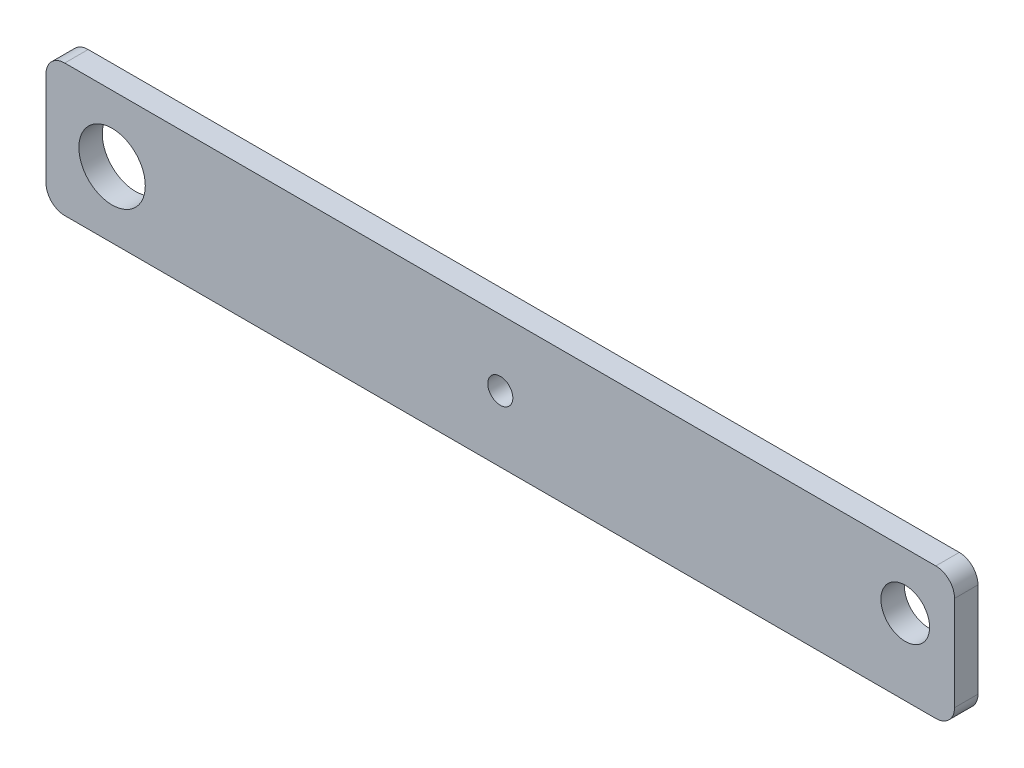
SolidWorks part; units mm, degrees
material "1100-H12 Rod (SS)"
ref_plane "X-Y Datum" through (0, 0, 0) normal (0, 0, 1) x (1, 0, 0)
ref_plane "X-Z Datum" through (0, 0, 0) normal (0, 1, 0) x (1, 0, 0)
ref_plane "Y-Z Datum" through (0, 0, 0) normal (1, 0, 0) x (0, 0, -1)
sketch "Sketch1" plane through (0, 0, 0) normal (0, 0, 1) x (1, 0, 0)
  line L9 (-48.0718, 5.3622) -> (75.004, 5.3622)
  line L10 (-48.0718, 5.3622) -> (-48.0718, 23.2622)
  line L11 (-48.0718, 23.2622) -> (75.004, 23.2622)
  line L12 (75.004, 5.3622) -> (75.004, 23.2622)
  circle A0 centre (-39.1218, 14.3122) radius 2
  circle A1 centre (68.3238, 15.6357) radius 2.54
base flange "Base-Flange1" sketch "Sketch1" thickness 3.175 reverse thickness direction no parameters "D1"=9.525
fillet "Fillet1" radius 2.54 4 edges at (-48.0718, 23.2622, -1.5875) (-48.0718, 5.3622, -1.5875) (75.004, 5.3622, -1.5875) (75.004, 23.2622, -1.5875)
hole_wizard "M8 Clearance Hole1" positions "Sketch6" profile "Sketch7" hole size "M8" standard "ANSI Metric" end condition through all
sketch "Sketch6" plane through (0, 0, 0) normal (0, 0, 1) x (1, 0, 0)
  point P0 (-39.1218, 14.3122)
sketch "Sketch7" plane through (-39.1218, 14.3122, 0) normal (1, 0, 0) x (0, -1, 0)
  line L0 (0, 0) -> (0, 3.175)
  line L1 (0, 3.175) -> (4.5, 3.175)
  line L2 (4.5, 3.175) -> (4.5, 0)
  line L5 (4.5, 0) -> (0, 0)
  line L11 (0, -6.35) -> (0, 107.95) construction
  dimension "Thru Hole Dia." = 9
  dimension "Thru Hole Depth" = 3.175
hole_wizard "M6 Clearance Hole1" positions "Sketch8" profile "Sketch9" hole size "M6" standard "ANSI Metric" end condition through all
sketch "Sketch8" plane through (0, 0, 0) normal (0, 0, 1) x (1, 0, 0)
  point P0 (68.3238, 15.6357)
sketch "Sketch9" plane through (68.3238, 15.6357, 0) normal (1, 0, 0) x (0, -1, 0)
  line L0 (0, 0) -> (0, 3.175)
  line L1 (0, 3.175) -> (3.3, 3.175)
  line L2 (3.3, 3.175) -> (3.3, 0)
  line L5 (3.3, 0) -> (0, 0)
  line L11 (0, -6.35) -> (0, 107.95) construction
  dimension "Thru Hole Dia." = 6.6
  dimension "Thru Hole Depth" = 3.175
sketch "Sketch10" plane through (0, 0, 0) normal (0, 0, 1) x (1, 0, 0)
  line L0 (13.4661, 23.2622) -> (13.4661, 5.3622) construction
  line L1 (72.464, 23.2622) -> (-45.5318, 23.2622) construction
  line L2 (-45.5318, 5.3622) -> (72.464, 5.3622) construction
  circle A0 centre (13.4661, 14.3122) radius 1
extrude "Cut-Extrude1" cut sketch "Sketch10" against normal through all normal cut yes
hole_wizard "M3 Clearance Hole2" positions "Sketch13" profile "Sketch14" hole size "M3" standard "ANSI Metric" end condition through all
sketch "Sketch13" plane through (0, 0, 0) normal (0, 0, 1) x (1, 0, 0)
  point P0 (13.4661, 14.3122)
sketch "Sketch14" plane through (13.4661, 14.3122, 0) normal (1, 0, 0) x (0, -1, 0)
  line L0 (0, 0) -> (0, 3.175)
  line L1 (0, 3.175) -> (1.7, 3.175)
  line L2 (1.7, 3.175) -> (1.7, 0)
  line L5 (1.7, 0) -> (0, 0)
  line L11 (0, -6.35) -> (0, 107.95) construction
  dimension "Thru Hole Dia." = 3.4
  dimension "Thru Hole Depth" = 3.175
sketch "Bend-Lines1" [suppressed] plane through (0, 0, 0) normal (0, 1, 0) x (1, 0, 0)
sketch "Bounding-Box1" [suppressed] plane through (0, 0, 0) normal (0, 1, 0) x (1, 0, 0)
sheet metal parameters "Sheet-Metal1" thickness 3.175 parameters "D1"=9.525
flat pattern "Flat-Pattern1" [suppressed]
sketch "Bend-Lines2" plane through (0, 0, 0) normal (0, 1, 0) x (1, 0, 0)
sketch3d "Bounding-Box2" [suppressed]
  line L0 (-48.0718, 5.3622, 0) -> (75.004, 5.3622, 0) construction
  line L1 (-48.0718, 23.2622, 0) -> (75.004, 23.2622, 0) construction
  line L2 (-48.0718, 5.3622, 0) -> (-48.0718, 23.2622, 0) construction
  line L3 (75.004, 5.3622, 0) -> (75.004, 23.2622, 0) construction
sheet metal parameters "Sheet-Metal2" thickness 3.175 parameters "D1"=9.525
flat pattern "Flat-Pattern1"
sketch "Bend-Lines2" plane through (0, 0, 0) normal (0, 1, 0) x (1, 0, 0)
sketch3d "Bounding-Box2" [suppressed]
  line L0 (-48.0718, 5.3622, 0) -> (75.004, 5.3622, 0) construction
  line L1 (-48.0718, 23.2622, 0) -> (75.004, 23.2622, 0) construction
  line L2 (-48.0718, 5.3622, 0) -> (-48.0718, 23.2622, 0) construction
  line L3 (75.004, 5.3622, 0) -> (75.004, 23.2622, 0) construction
sheet metal parameters "Sheet-Metal3" thickness 3.175 parameters "D1"=9.525
flat pattern "Flat-Pattern1"
sketch "Bend-Lines2" plane through (0, 0, 0) normal (0, 1, 0) x (1, 0, 0)
sketch3d "Bounding-Box2" [suppressed]
  line L0 (-48.0718, 5.3622, 0) -> (75.004, 5.3622, 0) construction
  line L1 (-48.0718, 23.2622, 0) -> (75.004, 23.2622, 0) construction
  line L2 (-48.0718, 5.3622, 0) -> (-48.0718, 23.2622, 0) construction
  line L3 (75.004, 5.3622, 0) -> (75.004, 23.2622, 0) construction
sheet metal parameters "Sheet-Metal4" thickness 3.175 parameters "D1"=9.525
flat pattern "Flat-Pattern1"
sketch "Bend-Lines2" plane through (0, 0, 0) normal (0, 1, 0) x (1, 0, 0)
sketch3d "Bounding-Box2" [suppressed]
  line L0 (-48.0718, 5.3622, 0) -> (75.004, 5.3622, 0) construction
  line L1 (-48.0718, 23.2622, 0) -> (75.004, 23.2622, 0) construction
  line L2 (-48.0718, 5.3622, 0) -> (-48.0718, 23.2622, 0) construction
  line L3 (75.004, 5.3622, 0) -> (75.004, 23.2622, 0) construction
sheet metal parameters "Sheet-Metal5" thickness 3.175 parameters "D1"=9.525
flat pattern "Flat-Pattern1"
sketch "Bend-Lines2" plane through (0, 0, 0) normal (0, 1, 0) x (1, 0, 0)
sketch3d "Bounding-Box2" [suppressed]
  line L0 (-48.0718, 5.3622, 0) -> (75.004, 5.3622, 0) construction
  line L1 (-48.0718, 23.2622, 0) -> (75.004, 23.2622, 0) construction
  line L2 (-48.0718, 5.3622, 0) -> (-48.0718, 23.2622, 0) construction
  line L3 (75.004, 5.3622, 0) -> (75.004, 23.2622, 0) construction
